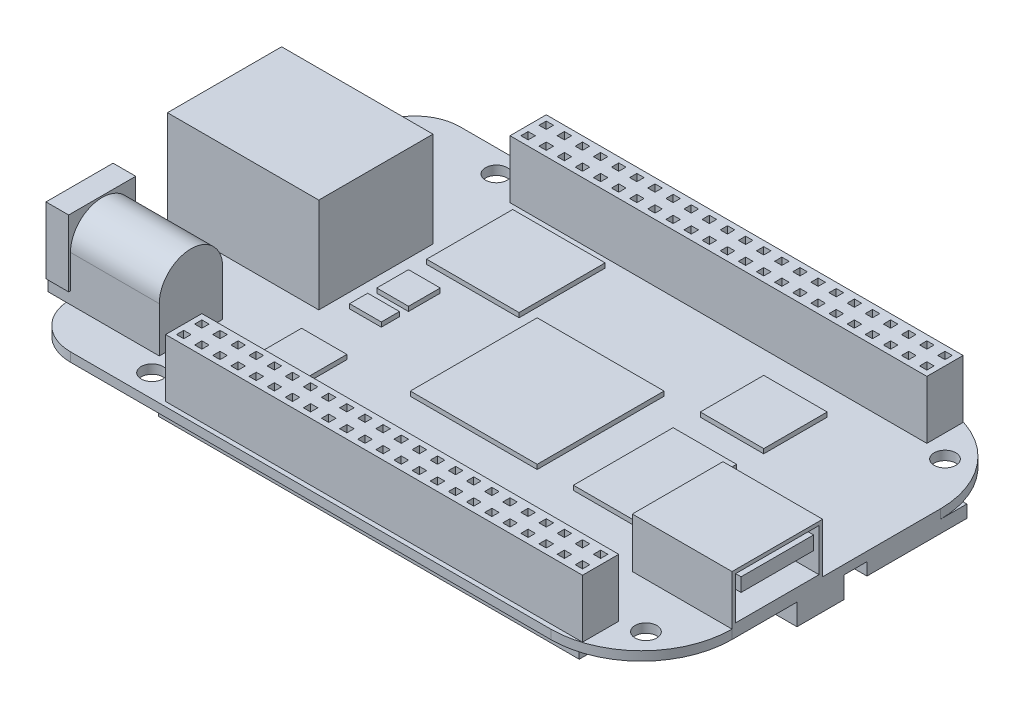
SolidWorks part; units mm, degrees
material "beaglebone"
ref_plane "Front Plane" through (0, 0, 0) normal (0, 0, 1) x (1, 0, 0)
ref_plane "Top Plane" through (0, 0, 0) normal (0, 1, 0) x (1, 0, 0)
ref_plane "Right Plane" through (0, 0, 0) normal (1, 0, 0) x (0, 0, -1)
sketch "Sketch1" plane through (0, 0, 0) normal (0, 1, 0) x (1, 0, 0)
  line L1 (-12.7, 0) -> (-80.01, 0)
  line L2 (0, 12.7) -> (0, 41.91)
  line L3 (-12.7, 54.61) -> (-80.01, 54.61)
  line L4 (-86.36, 6.35) -> (-86.36, 48.26)
  arc A0 (0, 12.7) -> (-12.7, 0) centre (-12.7, 12.7) cw
  arc A1 (0, 41.91) -> (-12.7, 54.61) centre (-12.7, 41.91) ccw
  arc A2 (-86.36, 6.35) -> (-80.01, 0) centre (-80.01, 6.35) ccw
  arc A3 (-86.36, 48.26) -> (-80.01, 54.61) centre (-80.01, 48.26) cw
  point P7 (0, 0)
  point P10 (0, 54.61)
  point P13 (-86.36, 0)
  dimension "D3" = 12.7
  dimension "D4" = 6.35
  dimension "D1" = 86.36
  dimension "D2" = 54.61
extrude "Boss-Extrude1" add sketch "Sketch1" along normal blind 1.27
sketch "Sketch2" plane through (0, 1.27, 0) normal (0, 1, 0) x (1, 0, 0)
  line L0 (-80.01, 0) -> (-12.7, 0) construction
  line L1 (-5.715, 6.35) -> (-71.755, 6.35) construction
  line L2 (-71.755, 51.435) -> (-71.755, 3.175) construction
  line L3 (-86.36, 48.26) -> (-86.36, 6.35) construction
  line L4 (-5.715, 48.26) -> (-5.715, 6.35) construction
  circle A0 centre (-71.755, 51.435) radius 1.524
  circle A1 centre (-71.755, 3.175) radius 1.524
  circle A2 centre (-5.715, 48.26) radius 1.524
  circle A3 centre (-5.715, 6.35) radius 1.524
  dimension "D7" = 3.048
  dimension "D1" = 48.26
  dimension "D2" = 41.91
  dimension "D3" = 6.35
  dimension "D4" = 14.605
  dimension "D5" = 80.645
  dimension "D6" = 3.175
extrude "Cut-Extrude1" cut sketch "Sketch2" along direction (0, -1, 0) on the side against the normal up to surface (1.27 mm away) up to face at (-44.4387, 0, -27.305)
sketch "Sketch3" plane through (0, 1.27, 0) normal (0, 1, 0) x (1, 0, 0)
  line L0 (-10.16, 48.895) -> (-10.16, 50.165) construction
  line L1 (-67.31, 53.975) -> (-8.89, 53.975)
  line L2 (-67.31, 53.975) -> (-67.31, 48.895)
  line L3 (-67.31, 48.895) -> (-8.89, 48.895)
  line L4 (-8.89, 53.975) -> (-8.89, 48.895)
  line L5 (-86.36, 27.305) -> (0, 27.305) construction
  line L6 (0, 12.7) -> (0, 41.91) construction
  line L7 (-66.548, 4.953) -> (-66.548, 3.937)
  line L8 (-66.548, 4.953) -> (-65.532, 4.953)
  line L9 (-10.16, 50.165) -> (-10.16, 52.705) construction
  line L10 (-10.16, 52.705) -> (-10.16, 53.975) construction
  line L11 (-13.208, 52.197) -> (-12.192, 52.197)
  line L12 (-10.668, 53.213) -> (-9.652, 53.213)
  line L13 (-10.668, 53.213) -> (-10.668, 52.197)
  line L14 (-10.668, 52.197) -> (-9.652, 52.197)
  line L15 (-9.652, 53.213) -> (-9.652, 52.197)
  line L16 (-10.668, 53.213) -> (-9.652, 52.197) construction
  line L17 (-10.668, 52.197) -> (-9.652, 53.213) construction
  line L18 (-10.668, 49.657) -> (-9.652, 49.657)
  line L19 (-10.668, 49.657) -> (-10.668, 50.673)
  line L20 (-10.668, 50.673) -> (-9.652, 50.673)
  line L21 (-9.652, 49.657) -> (-9.652, 50.673)
  line L22 (-10.668, 49.657) -> (-9.652, 50.673) construction
  line L23 (-10.668, 50.673) -> (-9.652, 49.657) construction
  line L24 (-13.208, 53.213) -> (-13.208, 52.197)
  line L25 (-13.208, 53.213) -> (-12.192, 53.213)
  line L26 (-12.192, 53.213) -> (-12.192, 52.197)
  line L27 (-13.208, 50.673) -> (-12.192, 50.673)
  line L28 (-12.192, 49.657) -> (-12.192, 50.673)
  line L29 (-13.208, 49.657) -> (-12.192, 49.657)
  line L30 (-13.208, 49.657) -> (-13.208, 50.673)
  line L31 (-15.748, 52.197) -> (-14.732, 52.197)
  line L32 (-15.748, 53.213) -> (-15.748, 52.197)
  line L33 (-15.748, 53.213) -> (-14.732, 53.213)
  line L34 (-14.732, 53.213) -> (-14.732, 52.197)
  line L35 (-15.748, 50.673) -> (-14.732, 50.673)
  line L36 (-14.732, 49.657) -> (-14.732, 50.673)
  line L37 (-15.748, 49.657) -> (-14.732, 49.657)
  line L38 (-15.748, 49.657) -> (-15.748, 50.673)
  line L39 (-18.288, 52.197) -> (-17.272, 52.197)
  line L40 (-18.288, 53.213) -> (-18.288, 52.197)
  line L41 (-18.288, 53.213) -> (-17.272, 53.213)
  line L42 (-17.272, 53.213) -> (-17.272, 52.197)
  line L43 (-18.288, 50.673) -> (-17.272, 50.673)
  line L44 (-17.272, 49.657) -> (-17.272, 50.673)
  line L45 (-18.288, 49.657) -> (-17.272, 49.657)
  line L46 (-18.288, 49.657) -> (-18.288, 50.673)
  line L47 (-20.828, 52.197) -> (-19.812, 52.197)
  line L48 (-20.828, 53.213) -> (-20.828, 52.197)
  line L49 (-20.828, 53.213) -> (-19.812, 53.213)
  line L50 (-19.812, 53.213) -> (-19.812, 52.197)
  line L51 (-20.828, 50.673) -> (-19.812, 50.673)
  line L52 (-19.812, 49.657) -> (-19.812, 50.673)
  line L53 (-20.828, 49.657) -> (-19.812, 49.657)
  line L54 (-20.828, 49.657) -> (-20.828, 50.673)
  line L55 (-23.368, 52.197) -> (-22.352, 52.197)
  line L56 (-23.368, 53.213) -> (-23.368, 52.197)
  line L57 (-23.368, 53.213) -> (-22.352, 53.213)
  line L58 (-22.352, 53.213) -> (-22.352, 52.197)
  line L59 (-23.368, 50.673) -> (-22.352, 50.673)
  line L60 (-22.352, 49.657) -> (-22.352, 50.673)
  line L61 (-23.368, 49.657) -> (-22.352, 49.657)
  line L62 (-23.368, 49.657) -> (-23.368, 50.673)
  line L63 (-25.908, 52.197) -> (-24.892, 52.197)
  line L64 (-25.908, 53.213) -> (-25.908, 52.197)
  line L65 (-25.908, 53.213) -> (-24.892, 53.213)
  line L66 (-24.892, 53.213) -> (-24.892, 52.197)
  line L67 (-25.908, 50.673) -> (-24.892, 50.673)
  line L68 (-24.892, 49.657) -> (-24.892, 50.673)
  line L69 (-25.908, 49.657) -> (-24.892, 49.657)
  line L70 (-25.908, 49.657) -> (-25.908, 50.673)
  line L71 (-28.448, 52.197) -> (-27.432, 52.197)
  line L72 (-28.448, 53.213) -> (-28.448, 52.197)
  line L73 (-28.448, 53.213) -> (-27.432, 53.213)
  line L74 (-27.432, 53.213) -> (-27.432, 52.197)
  line L75 (-28.448, 50.673) -> (-27.432, 50.673)
  line L76 (-27.432, 49.657) -> (-27.432, 50.673)
  line L77 (-28.448, 49.657) -> (-27.432, 49.657)
  line L78 (-28.448, 49.657) -> (-28.448, 50.673)
  line L79 (-30.988, 52.197) -> (-29.972, 52.197)
  line L80 (-30.988, 53.213) -> (-30.988, 52.197)
  line L81 (-30.988, 53.213) -> (-29.972, 53.213)
  line L82 (-29.972, 53.213) -> (-29.972, 52.197)
  line L83 (-30.988, 50.673) -> (-29.972, 50.673)
  line L84 (-29.972, 49.657) -> (-29.972, 50.673)
  line L85 (-30.988, 49.657) -> (-29.972, 49.657)
  line L86 (-30.988, 49.657) -> (-30.988, 50.673)
  line L87 (-33.528, 52.197) -> (-32.512, 52.197)
  line L88 (-33.528, 53.213) -> (-33.528, 52.197)
  line L89 (-33.528, 53.213) -> (-32.512, 53.213)
  line L90 (-32.512, 53.213) -> (-32.512, 52.197)
  line L91 (-33.528, 50.673) -> (-32.512, 50.673)
  line L92 (-32.512, 49.657) -> (-32.512, 50.673)
  line L93 (-33.528, 49.657) -> (-32.512, 49.657)
  line L94 (-33.528, 49.657) -> (-33.528, 50.673)
  line L95 (-36.068, 52.197) -> (-35.052, 52.197)
  line L96 (-36.068, 53.213) -> (-36.068, 52.197)
  line L97 (-36.068, 53.213) -> (-35.052, 53.213)
  line L98 (-35.052, 53.213) -> (-35.052, 52.197)
  line L99 (-36.068, 50.673) -> (-35.052, 50.673)
  line L100 (-35.052, 49.657) -> (-35.052, 50.673)
  line L101 (-36.068, 49.657) -> (-35.052, 49.657)
  line L102 (-36.068, 49.657) -> (-36.068, 50.673)
  line L103 (-38.608, 52.197) -> (-37.592, 52.197)
  line L104 (-38.608, 53.213) -> (-38.608, 52.197)
  line L105 (-38.608, 53.213) -> (-37.592, 53.213)
  line L106 (-37.592, 53.213) -> (-37.592, 52.197)
  line L107 (-38.608, 50.673) -> (-37.592, 50.673)
  line L108 (-37.592, 49.657) -> (-37.592, 50.673)
  line L109 (-38.608, 49.657) -> (-37.592, 49.657)
  line L110 (-38.608, 49.657) -> (-38.608, 50.673)
  line L111 (-41.148, 52.197) -> (-40.132, 52.197)
  line L112 (-41.148, 53.213) -> (-41.148, 52.197)
  line L113 (-41.148, 53.213) -> (-40.132, 53.213)
  line L114 (-40.132, 53.213) -> (-40.132, 52.197)
  line L115 (-41.148, 50.673) -> (-40.132, 50.673)
  line L116 (-40.132, 49.657) -> (-40.132, 50.673)
  line L117 (-41.148, 49.657) -> (-40.132, 49.657)
  line L118 (-41.148, 49.657) -> (-41.148, 50.673)
  line L119 (-43.688, 52.197) -> (-42.672, 52.197)
  line L120 (-43.688, 53.213) -> (-43.688, 52.197)
  line L121 (-43.688, 53.213) -> (-42.672, 53.213)
  line L122 (-42.672, 53.213) -> (-42.672, 52.197)
  line L123 (-43.688, 50.673) -> (-42.672, 50.673)
  line L124 (-42.672, 49.657) -> (-42.672, 50.673)
  line L125 (-43.688, 49.657) -> (-42.672, 49.657)
  line L126 (-43.688, 49.657) -> (-43.688, 50.673)
  line L127 (-46.228, 52.197) -> (-45.212, 52.197)
  line L128 (-46.228, 53.213) -> (-46.228, 52.197)
  line L129 (-46.228, 53.213) -> (-45.212, 53.213)
  line L130 (-45.212, 53.213) -> (-45.212, 52.197)
  line L131 (-46.228, 50.673) -> (-45.212, 50.673)
  line L132 (-45.212, 49.657) -> (-45.212, 50.673)
  line L133 (-46.228, 49.657) -> (-45.212, 49.657)
  line L134 (-46.228, 49.657) -> (-46.228, 50.673)
  line L135 (-48.768, 52.197) -> (-47.752, 52.197)
  line L136 (-48.768, 53.213) -> (-48.768, 52.197)
  line L137 (-48.768, 53.213) -> (-47.752, 53.213)
  line L138 (-47.752, 53.213) -> (-47.752, 52.197)
  line L139 (-48.768, 50.673) -> (-47.752, 50.673)
  line L140 (-47.752, 49.657) -> (-47.752, 50.673)
  line L141 (-48.768, 49.657) -> (-47.752, 49.657)
  line L142 (-48.768, 49.657) -> (-48.768, 50.673)
  line L143 (-51.308, 52.197) -> (-50.292, 52.197)
  line L144 (-51.308, 53.213) -> (-51.308, 52.197)
  line L145 (-51.308, 53.213) -> (-50.292, 53.213)
  line L146 (-50.292, 53.213) -> (-50.292, 52.197)
  line L147 (-51.308, 50.673) -> (-50.292, 50.673)
  line L148 (-50.292, 49.657) -> (-50.292, 50.673)
  line L149 (-51.308, 49.657) -> (-50.292, 49.657)
  line L150 (-51.308, 49.657) -> (-51.308, 50.673)
  line L151 (-53.848, 52.197) -> (-52.832, 52.197)
  line L152 (-53.848, 53.213) -> (-53.848, 52.197)
  line L153 (-53.848, 53.213) -> (-52.832, 53.213)
  line L154 (-52.832, 53.213) -> (-52.832, 52.197)
  line L155 (-53.848, 50.673) -> (-52.832, 50.673)
  line L156 (-52.832, 49.657) -> (-52.832, 50.673)
  line L157 (-53.848, 49.657) -> (-52.832, 49.657)
  line L158 (-53.848, 49.657) -> (-53.848, 50.673)
  line L159 (-56.388, 52.197) -> (-55.372, 52.197)
  line L160 (-56.388, 53.213) -> (-56.388, 52.197)
  line L161 (-56.388, 53.213) -> (-55.372, 53.213)
  line L162 (-55.372, 53.213) -> (-55.372, 52.197)
  line L163 (-56.388, 50.673) -> (-55.372, 50.673)
  line L164 (-55.372, 49.657) -> (-55.372, 50.673)
  line L165 (-56.388, 49.657) -> (-55.372, 49.657)
  line L166 (-56.388, 49.657) -> (-56.388, 50.673)
  line L167 (-58.928, 52.197) -> (-57.912, 52.197)
  line L168 (-58.928, 53.213) -> (-58.928, 52.197)
  line L169 (-58.928, 53.213) -> (-57.912, 53.213)
  line L170 (-57.912, 53.213) -> (-57.912, 52.197)
  line L171 (-58.928, 50.673) -> (-57.912, 50.673)
  line L172 (-57.912, 49.657) -> (-57.912, 50.673)
  line L173 (-58.928, 49.657) -> (-57.912, 49.657)
  line L174 (-58.928, 49.657) -> (-58.928, 50.673)
  line L175 (-61.468, 52.197) -> (-60.452, 52.197)
  line L176 (-61.468, 53.213) -> (-61.468, 52.197)
  line L177 (-61.468, 53.213) -> (-60.452, 53.213)
  line L178 (-60.452, 53.213) -> (-60.452, 52.197)
  line L179 (-61.468, 50.673) -> (-60.452, 50.673)
  line L180 (-60.452, 49.657) -> (-60.452, 50.673)
  line L181 (-61.468, 49.657) -> (-60.452, 49.657)
  line L182 (-61.468, 49.657) -> (-61.468, 50.673)
  line L183 (-64.008, 52.197) -> (-62.992, 52.197)
  line L184 (-64.008, 53.213) -> (-64.008, 52.197)
  line L185 (-64.008, 53.213) -> (-62.992, 53.213)
  line L186 (-62.992, 53.213) -> (-62.992, 52.197)
  line L187 (-64.008, 50.673) -> (-62.992, 50.673)
  line L188 (-62.992, 49.657) -> (-62.992, 50.673)
  line L189 (-64.008, 49.657) -> (-62.992, 49.657)
  line L190 (-64.008, 49.657) -> (-64.008, 50.673)
  line L191 (-66.548, 52.197) -> (-65.532, 52.197)
  line L192 (-66.548, 53.213) -> (-66.548, 52.197)
  line L193 (-66.548, 53.213) -> (-65.532, 53.213)
  line L194 (-65.532, 53.213) -> (-65.532, 52.197)
  line L195 (-66.548, 50.673) -> (-65.532, 50.673)
  line L196 (-65.532, 49.657) -> (-65.532, 50.673)
  line L197 (-66.548, 49.657) -> (-65.532, 49.657)
  line L198 (-66.548, 49.657) -> (-66.548, 50.673)
  line L199 (-66.548, 49.657) -> (-65.532, 50.673) construction
  line L200 (-86.36, 48.26) -> (-86.36, 6.35) construction
  line L201 (-65.532, 4.953) -> (-65.532, 3.937)
  line L202 (-12.7, 54.61) -> (-80.01, 54.61) construction
  line L203 (-66.548, 3.937) -> (-65.532, 3.937)
  line L204 (-65.532, 1.397) -> (-65.532, 2.413)
  line L205 (-66.548, 1.397) -> (-65.532, 1.397)
  line L206 (-66.548, 1.397) -> (-66.548, 2.413)
  line L207 (-66.548, 2.413) -> (-65.532, 2.413)
  line L208 (-64.008, 4.953) -> (-64.008, 3.937)
  line L209 (-64.008, 4.953) -> (-62.992, 4.953)
  line L210 (-62.992, 4.953) -> (-62.992, 3.937)
  line L211 (-64.008, 3.937) -> (-62.992, 3.937)
  line L212 (-62.992, 1.397) -> (-62.992, 2.413)
  line L213 (-64.008, 1.397) -> (-62.992, 1.397)
  line L214 (-64.008, 1.397) -> (-64.008, 2.413)
  line L215 (-64.008, 2.413) -> (-62.992, 2.413)
  line L216 (-61.468, 4.953) -> (-61.468, 3.937)
  line L217 (-61.468, 4.953) -> (-60.452, 4.953)
  line L218 (-60.452, 4.953) -> (-60.452, 3.937)
  line L219 (-61.468, 3.937) -> (-60.452, 3.937)
  line L220 (-60.452, 1.397) -> (-60.452, 2.413)
  line L221 (-61.468, 1.397) -> (-60.452, 1.397)
  line L222 (-61.468, 1.397) -> (-61.468, 2.413)
  line L223 (-61.468, 2.413) -> (-60.452, 2.413)
  line L224 (-58.928, 4.953) -> (-58.928, 3.937)
  line L225 (-58.928, 4.953) -> (-57.912, 4.953)
  line L226 (-57.912, 4.953) -> (-57.912, 3.937)
  line L227 (-58.928, 3.937) -> (-57.912, 3.937)
  line L228 (-57.912, 1.397) -> (-57.912, 2.413)
  line L229 (-58.928, 1.397) -> (-57.912, 1.397)
  line L230 (-58.928, 1.397) -> (-58.928, 2.413)
  line L231 (-58.928, 2.413) -> (-57.912, 2.413)
  line L232 (-56.388, 4.953) -> (-56.388, 3.937)
  line L233 (-56.388, 4.953) -> (-55.372, 4.953)
  line L234 (-55.372, 4.953) -> (-55.372, 3.937)
  line L235 (-56.388, 3.937) -> (-55.372, 3.937)
  line L236 (-55.372, 1.397) -> (-55.372, 2.413)
  line L237 (-56.388, 1.397) -> (-55.372, 1.397)
  line L238 (-56.388, 1.397) -> (-56.388, 2.413)
  line L239 (-56.388, 2.413) -> (-55.372, 2.413)
  line L240 (-53.848, 4.953) -> (-53.848, 3.937)
  line L241 (-53.848, 4.953) -> (-52.832, 4.953)
  line L242 (-52.832, 4.953) -> (-52.832, 3.937)
  line L243 (-53.848, 3.937) -> (-52.832, 3.937)
  line L244 (-52.832, 1.397) -> (-52.832, 2.413)
  line L245 (-53.848, 1.397) -> (-52.832, 1.397)
  line L246 (-53.848, 1.397) -> (-53.848, 2.413)
  line L247 (-53.848, 2.413) -> (-52.832, 2.413)
  line L248 (-51.308, 4.953) -> (-51.308, 3.937)
  line L249 (-51.308, 4.953) -> (-50.292, 4.953)
  line L250 (-50.292, 4.953) -> (-50.292, 3.937)
  line L251 (-51.308, 3.937) -> (-50.292, 3.937)
  line L252 (-50.292, 1.397) -> (-50.292, 2.413)
  line L253 (-51.308, 1.397) -> (-50.292, 1.397)
  line L254 (-51.308, 1.397) -> (-51.308, 2.413)
  line L255 (-51.308, 2.413) -> (-50.292, 2.413)
  line L256 (-48.768, 4.953) -> (-48.768, 3.937)
  line L257 (-48.768, 4.953) -> (-47.752, 4.953)
  line L258 (-47.752, 4.953) -> (-47.752, 3.937)
  line L259 (-48.768, 3.937) -> (-47.752, 3.937)
  line L260 (-47.752, 1.397) -> (-47.752, 2.413)
  line L261 (-48.768, 1.397) -> (-47.752, 1.397)
  line L262 (-48.768, 1.397) -> (-48.768, 2.413)
  line L263 (-48.768, 2.413) -> (-47.752, 2.413)
  line L264 (-46.228, 4.953) -> (-46.228, 3.937)
  line L265 (-46.228, 4.953) -> (-45.212, 4.953)
  line L266 (-45.212, 4.953) -> (-45.212, 3.937)
  line L267 (-46.228, 3.937) -> (-45.212, 3.937)
  line L268 (-45.212, 1.397) -> (-45.212, 2.413)
  line L269 (-46.228, 1.397) -> (-45.212, 1.397)
  line L270 (-46.228, 1.397) -> (-46.228, 2.413)
  line L271 (-46.228, 2.413) -> (-45.212, 2.413)
  line L272 (-43.688, 4.953) -> (-43.688, 3.937)
  line L273 (-43.688, 4.953) -> (-42.672, 4.953)
  line L274 (-42.672, 4.953) -> (-42.672, 3.937)
  line L275 (-43.688, 3.937) -> (-42.672, 3.937)
  line L276 (-42.672, 1.397) -> (-42.672, 2.413)
  line L277 (-43.688, 1.397) -> (-42.672, 1.397)
  line L278 (-43.688, 1.397) -> (-43.688, 2.413)
  line L279 (-43.688, 2.413) -> (-42.672, 2.413)
  line L280 (-41.148, 4.953) -> (-41.148, 3.937)
  line L281 (-41.148, 4.953) -> (-40.132, 4.953)
  line L282 (-40.132, 4.953) -> (-40.132, 3.937)
  line L283 (-41.148, 3.937) -> (-40.132, 3.937)
  line L284 (-40.132, 1.397) -> (-40.132, 2.413)
  line L285 (-41.148, 1.397) -> (-40.132, 1.397)
  line L286 (-41.148, 1.397) -> (-41.148, 2.413)
  line L287 (-41.148, 2.413) -> (-40.132, 2.413)
  line L288 (-38.608, 4.953) -> (-38.608, 3.937)
  line L289 (-38.608, 4.953) -> (-37.592, 4.953)
  line L290 (-37.592, 4.953) -> (-37.592, 3.937)
  line L291 (-38.608, 3.937) -> (-37.592, 3.937)
  line L292 (-37.592, 1.397) -> (-37.592, 2.413)
  line L293 (-38.608, 1.397) -> (-37.592, 1.397)
  line L294 (-38.608, 1.397) -> (-38.608, 2.413)
  line L295 (-38.608, 2.413) -> (-37.592, 2.413)
  line L296 (-36.068, 4.953) -> (-36.068, 3.937)
  line L297 (-36.068, 4.953) -> (-35.052, 4.953)
  line L298 (-35.052, 4.953) -> (-35.052, 3.937)
  line L299 (-36.068, 3.937) -> (-35.052, 3.937)
  line L300 (-35.052, 1.397) -> (-35.052, 2.413)
  line L301 (-36.068, 1.397) -> (-35.052, 1.397)
  line L302 (-36.068, 1.397) -> (-36.068, 2.413)
  line L303 (-36.068, 2.413) -> (-35.052, 2.413)
  line L304 (-33.528, 4.953) -> (-33.528, 3.937)
  line L305 (-33.528, 4.953) -> (-32.512, 4.953)
  line L306 (-32.512, 4.953) -> (-32.512, 3.937)
  line L307 (-33.528, 3.937) -> (-32.512, 3.937)
  line L308 (-32.512, 1.397) -> (-32.512, 2.413)
  line L309 (-33.528, 1.397) -> (-32.512, 1.397)
  line L310 (-33.528, 1.397) -> (-33.528, 2.413)
  line L311 (-33.528, 2.413) -> (-32.512, 2.413)
  line L312 (-30.988, 4.953) -> (-30.988, 3.937)
  line L313 (-30.988, 4.953) -> (-29.972, 4.953)
  line L314 (-29.972, 4.953) -> (-29.972, 3.937)
  line L315 (-30.988, 3.937) -> (-29.972, 3.937)
  line L316 (-29.972, 1.397) -> (-29.972, 2.413)
  line L317 (-30.988, 1.397) -> (-29.972, 1.397)
  line L318 (-30.988, 1.397) -> (-30.988, 2.413)
  line L319 (-30.988, 2.413) -> (-29.972, 2.413)
  line L320 (-28.448, 4.953) -> (-28.448, 3.937)
  line L321 (-28.448, 4.953) -> (-27.432, 4.953)
  line L322 (-27.432, 4.953) -> (-27.432, 3.937)
  line L323 (-28.448, 3.937) -> (-27.432, 3.937)
  line L324 (-27.432, 1.397) -> (-27.432, 2.413)
  line L325 (-28.448, 1.397) -> (-27.432, 1.397)
  line L326 (-28.448, 1.397) -> (-28.448, 2.413)
  line L327 (-28.448, 2.413) -> (-27.432, 2.413)
  line L328 (-25.908, 4.953) -> (-25.908, 3.937)
  line L329 (-25.908, 4.953) -> (-24.892, 4.953)
  line L330 (-24.892, 4.953) -> (-24.892, 3.937)
  line L331 (-25.908, 3.937) -> (-24.892, 3.937)
  line L332 (-24.892, 1.397) -> (-24.892, 2.413)
  line L333 (-25.908, 1.397) -> (-24.892, 1.397)
  line L334 (-25.908, 1.397) -> (-25.908, 2.413)
  line L335 (-25.908, 2.413) -> (-24.892, 2.413)
  line L336 (-23.368, 4.953) -> (-23.368, 3.937)
  line L337 (-23.368, 4.953) -> (-22.352, 4.953)
  line L338 (-22.352, 4.953) -> (-22.352, 3.937)
  line L339 (-23.368, 3.937) -> (-22.352, 3.937)
  line L340 (-22.352, 1.397) -> (-22.352, 2.413)
  line L341 (-23.368, 1.397) -> (-22.352, 1.397)
  line L342 (-23.368, 1.397) -> (-23.368, 2.413)
  line L343 (-23.368, 2.413) -> (-22.352, 2.413)
  line L344 (-20.828, 4.953) -> (-20.828, 3.937)
  line L345 (-20.828, 4.953) -> (-19.812, 4.953)
  line L346 (-19.812, 4.953) -> (-19.812, 3.937)
  line L347 (-20.828, 3.937) -> (-19.812, 3.937)
  line L348 (-19.812, 1.397) -> (-19.812, 2.413)
  line L349 (-20.828, 1.397) -> (-19.812, 1.397)
  line L350 (-20.828, 1.397) -> (-20.828, 2.413)
  line L351 (-20.828, 2.413) -> (-19.812, 2.413)
  line L352 (-18.288, 4.953) -> (-18.288, 3.937)
  line L353 (-18.288, 4.953) -> (-17.272, 4.953)
  line L354 (-17.272, 4.953) -> (-17.272, 3.937)
  line L355 (-18.288, 3.937) -> (-17.272, 3.937)
  line L356 (-17.272, 1.397) -> (-17.272, 2.413)
  line L357 (-18.288, 1.397) -> (-17.272, 1.397)
  line L358 (-18.288, 1.397) -> (-18.288, 2.413)
  line L359 (-18.288, 2.413) -> (-17.272, 2.413)
  line L360 (-15.748, 4.953) -> (-15.748, 3.937)
  line L361 (-15.748, 4.953) -> (-14.732, 4.953)
  line L362 (-14.732, 4.953) -> (-14.732, 3.937)
  line L363 (-15.748, 3.937) -> (-14.732, 3.937)
  line L364 (-14.732, 1.397) -> (-14.732, 2.413)
  line L365 (-15.748, 1.397) -> (-14.732, 1.397)
  line L366 (-15.748, 1.397) -> (-15.748, 2.413)
  line L367 (-15.748, 2.413) -> (-14.732, 2.413)
  line L368 (-13.208, 4.953) -> (-13.208, 3.937)
  line L369 (-13.208, 4.953) -> (-12.192, 4.953)
  line L370 (-12.192, 4.953) -> (-12.192, 3.937)
  line L371 (-13.208, 3.937) -> (-12.192, 3.937)
  line L372 (-12.192, 1.397) -> (-12.192, 2.413)
  line L373 (-13.208, 1.397) -> (-12.192, 1.397)
  line L374 (-13.208, 1.397) -> (-13.208, 2.413)
  line L375 (-9.652, 4.953) -> (-9.652, 3.937)
  line L376 (-10.668, 3.937) -> (-9.652, 3.937)
  line L377 (-10.668, 4.953) -> (-10.668, 3.937)
  line L378 (-10.668, 4.953) -> (-9.652, 4.953)
  line L379 (-9.652, 1.397) -> (-9.652, 2.413)
  line L380 (-10.668, 2.413) -> (-9.652, 2.413)
  line L381 (-10.668, 1.397) -> (-10.668, 2.413)
  line L382 (-10.668, 1.397) -> (-9.652, 1.397)
  line L383 (-13.208, 2.413) -> (-12.192, 2.413)
  line L384 (-8.89, 0.635) -> (-8.89, 5.715)
  line L385 (-67.31, 5.715) -> (-8.89, 5.715)
  line L386 (-67.31, 0.635) -> (-67.31, 5.715)
  line L387 (-67.31, 0.635) -> (-8.89, 0.635)
  circle A0 centre (-66.04, 50.165) radius 0.1361
  dimension "D1" = 1.016
  dimension "D2" = 2.54
  dimension "D3" = 5.08
  dimension "D4" = 58.42
  dimension "D5" = 1.27
  dimension "D7" = 20.32
  dimension "D8" = 0.635
  dimension "D6" = 23
extrude "Boss-Extrude2" add sketch "Sketch3" along normal blind 8.128 contours L4 L1 L2 L3 L193 L194 L191 L192 L185 L186 L183 L184 L177 L178 L175 L176 L169 L170 L167 L168 L161 L162 L159 L160 L153 L154 L151 L152 L145 L146 L143 L144 L137 L138 L135 L136 L129 L130 L127 L128 L121 | L386 L387 L384 L385 L374 L383 L372 L373 L382 L381 L380 L379 L366 L367 L364 L365 L363 L360 L361 L362 L350 L351 L348 L349 L347 L344 L345 L346 L334 L335 L332 L333 L331 L328 L329 L330 L318 L319 L316 L317 L315 region at (-38.1, 1.27, -51.435) region at (-38.1, 1.27, -3.175)
sketch "Sketch4" plane through (0, 1.27, 0) normal (0, 1, 0) x (1, 0, 0)
  line L0 (-86.36, 48.26) -> (-86.36, 6.35) construction
  line L1 (-67.691, 22.479) -> (-88.9, 22.479)
  line L2 (-67.691, 22.479) -> (-67.691, 38.481)
  line L3 (-67.691, 38.481) -> (-88.9, 38.481)
  line L4 (-88.9, 22.479) -> (-88.9, 38.481)
  line L5 (-12.7, 54.61) -> (-80.01, 54.61) construction
  dimension "D1" = 2.54
  dimension "D2" = 21.209
  dimension "D3" = 16.002
  dimension "D4" = 16.129
extrude "Boss-Extrude3" add sketch "Sketch4" along normal blind 13.335
sketch "Sketch5" plane through (-88.9, 0, 0) normal (-1, 0, 0) x (0, 0, 1)
  line L0 (-30.48, 2.286) -> (-30.48, 3.937) construction
  line L1 (-36.83, 12.065) -> (-24.13, 12.065)
  line L2 (-36.83, 12.065) -> (-36.83, 5.461)
  line L3 (-36.83, 5.461) -> (-24.13, 5.461)
  line L4 (-24.13, 12.065) -> (-24.13, 5.461)
  line L5 (-33.655, 5.461) -> (-27.305, 5.461)
  line L6 (-33.655, 5.461) -> (-33.655, 3.937)
  line L7 (-33.655, 3.937) -> (-27.305, 3.937)
  line L8 (-27.305, 5.461) -> (-27.305, 3.937)
  line L9 (-32.512, 3.937) -> (-28.448, 3.937)
  line L10 (-32.512, 3.937) -> (-32.512, 2.286)
  line L11 (-32.512, 2.286) -> (-28.448, 2.286)
  line L12 (-28.448, 3.937) -> (-28.448, 2.286)
  line L13 (-30.48, 3.937) -> (-30.48, 5.461) construction
  line L14 (-38.481, 14.605) -> (-22.479, 14.605) construction
  line L15 (-36.83, 12.065) -> (-38.481, 12.065) construction
  line L16 (-38.481, 14.605) -> (-38.481, 1.27) construction
  line L17 (-24.13, 12.065) -> (-22.479, 12.065) construction
  line L18 (-22.479, 14.605) -> (-22.479, 1.27) construction
  dimension "D1" = 12.7
  dimension "D2" = 6.604
  dimension "D3" = 2.54
  dimension "D4" = 1.524
  dimension "D5" = 1.651
  dimension "D6" = 4.064
  dimension "D7" = 6.35
extrude "Cut-Extrude2" cut sketch "Sketch5" against normal blind 17.78 contours L4 L1 L2 L3 | L8 L3 L6 L7 | L12 L7 L10 L11 region at (-88.9, 8.763, -30.48) region at (-88.9, 4.699, -30.48) region at (-88.9, 3.1115, -30.48)
sketch "Sketch6" plane through (0, 1.27, 0) normal (0, 1, 0) x (1, 0, 0)
  line L0 (-67.31, 48.895) -> (-8.89, 48.895) construction
  line L1 (-65.659, 35.56) -> (-52.705, 35.56)
  line L2 (-65.659, 35.56) -> (-65.659, 47.625)
  line L3 (-65.659, 47.625) -> (-52.705, 47.625)
  line L4 (-52.705, 35.56) -> (-52.705, 47.625)
  line L5 (-50.8, 36.195) -> (-33.02, 36.195)
  line L6 (-50.8, 36.195) -> (-50.8, 18.415)
  line L7 (-50.8, 18.415) -> (-33.02, 18.415)
  line L8 (-33.02, 36.195) -> (-33.02, 18.415)
  line L9 (-27.94, 45.085) -> (-19.05, 45.085)
  line L10 (-27.94, 45.085) -> (-27.94, 36.195)
  line L11 (-27.94, 36.195) -> (-19.05, 36.195)
  line L12 (-19.05, 45.085) -> (-19.05, 36.195)
  line L13 (-27.94, 32.385) -> (-19.05, 32.385)
  line L14 (-27.94, 32.385) -> (-27.94, 18.415)
  line L15 (-27.94, 18.415) -> (-19.05, 18.415)
  line L16 (-19.05, 32.385) -> (-19.05, 18.415)
  line L17 (-66.04, 18.415) -> (-59.69, 18.415)
  line L18 (-66.04, 18.415) -> (-66.04, 12.065)
  line L19 (-66.04, 12.065) -> (-59.69, 12.065)
  line L20 (-59.69, 18.415) -> (-59.69, 12.065)
  line L21 (-65.659, 27.305) -> (-61.214, 27.305)
  line L22 (-65.659, 27.305) -> (-65.659, 24.765)
  line L23 (-65.659, 24.765) -> (-61.214, 24.765)
  line L24 (-61.214, 27.305) -> (-61.214, 24.765)
  line L25 (-65.659, 33.02) -> (-61.214, 33.02)
  line L26 (-65.659, 33.02) -> (-65.659, 28.575)
  line L27 (-65.659, 28.575) -> (-61.214, 28.575)
  line L28 (-61.214, 33.02) -> (-61.214, 28.575)
  line L29 (0, 12.7) -> (0, 41.91) construction
  line L30 (-67.31, 48.895) -> (-8.89, 48.895) construction
  line L31 (-67.31, 5.715) -> (-8.89, 5.715) construction
  line L33 (-67.31, 0.635) -> (-67.31, 5.715) construction
  dimension "D1" = 8.89
  dimension "D2" = 13.97
  dimension "D3" = 3.81
  dimension "D4" = 3.81
  dimension "D5" = 19.05
  dimension "D6" = 17.78
  dimension "D7" = 12.7
  dimension "D8" = 33.02
  dimension "D9" = 12.954
  dimension "D10" = 12.065
  dimension "D11" = 1.905
  dimension "D12" = 4.445
  dimension "D13" = 2.54
  dimension "D14" = 1.27
  dimension "D15" = 2.54
  dimension "D16" = 1.27
  dimension "D17" = 6.35
  dimension "D18" = 6.35
  dimension "D19" = 1.27
extrude "Boss-Extrude4" add sketch "Sketch6" along normal blind 0.635
sketch "Sketch7" plane through (0, 1.27, 0) normal (0, 1, 0) x (1, 0, 0)
  line L1 (0, 12.7) -> (-13.97, 12.7)
  line L2 (0, 12.7) -> (0, 25.4)
  line L3 (0, 25.4) -> (-13.97, 25.4)
  line L4 (-13.97, 12.7) -> (-13.97, 25.4)
  line L5 (-80.01, 0) -> (-12.7, 0) construction
  line L6 (0, 12.7) -> (0, 41.91) construction
  dimension "D1" = 12.7
  dimension "D2" = 13.97
  dimension "D3" = 25.4
extrude "Boss-Extrude5" add sketch "Sketch7" along normal blind 6.985
sketch "Sketch8" plane through (0, 0, 0) normal (1, 0, 0) x (0, 0, -1)
  line L0 (12.7, 8.255) -> (25.4, 8.255) construction
  line L1 (13.97, 6.985) -> (24.13, 6.985)
  line L2 (13.97, 6.985) -> (13.97, 5.08)
  line L3 (13.97, 5.08) -> (24.13, 5.08)
  line L4 (24.13, 6.985) -> (24.13, 5.08)
  line L5 (13.208, 7.747) -> (24.892, 7.747)
  line L6 (13.208, 7.747) -> (13.208, 1.778)
  line L7 (13.208, 1.778) -> (24.892, 1.778)
  line L8 (24.892, 7.747) -> (24.892, 1.778)
  line L9 (25.4, 8.255) -> (25.4, 1.27) construction
  line L10 (12.7, 8.255) -> (12.7, 1.27) construction
  line L11 (12.7, 1.27) -> (0, 1.27) construction
  line L12 (13.97, 7.18) -> (13.208, 7.18) construction
  line L14 (24.892, 6.9479) -> (24.13, 6.9479) construction
  dimension "D1" = 0.508
  dimension "D2" = 0.508
  dimension "D3" = 0.508
  dimension "D4" = 0.508
  dimension "D5" = 1.905
  dimension "D6" = 10.16
  dimension "D7" = 3.175
extrude "Cut-Extrude3" cut sketch "Sketch8" against normal blind 12.7
sketch "Sketch9" plane through (0, 1.27, 0) normal (0, 1, 0) x (1, 0, 0)
  line L0 (-88.9, 38.481) -> (-88.9, 22.479) construction
  line L1 (-73.279, 5.715) -> (-88.9, 5.715)
  line L2 (-73.279, 5.715) -> (-73.279, 14.605)
  line L3 (-73.279, 14.605) -> (-88.9, 14.605)
  line L4 (-88.9, 5.715) -> (-88.9, 14.605)
  line L5 (-67.31, 5.715) -> (-8.89, 5.715) construction
  circle A0 centre (-71.755, 3.175) radius 1.524 construction
  dimension "D1" = 8.89
extrude "Boss-Extrude6" add sketch "Sketch9" along normal blind 6.35
sketch "Sketch10" plane through (-88.9, 0, 0) normal (-1, 0, 0) x (0, 0, 1)
  line L0 (-14.605, 7.62) -> (-5.715, 7.62) construction
  circle A0 centre (-10.16, 7.62) radius 4.445
  circle A1 centre (-10.16, 7.62) radius 3.4925
  circle A2 centre (-10.16, 7.62) radius 0.635
  line M3 (-5.715, 7.62) -> (-14.605, 7.62)
  dimension "D1" = 1.27
  dimension "D2" = 6.985
extrude "Boss-Extrude7" add sketch "Sketch10" along direction (1, 0, 0) on the side against the normal up to surface (15.621 mm away) contours A1 A0 M3 | A1 A0 M3 | A2 M3 | A2 A1 M3 region at (-88.9, 7.7194, -6.1912) region at (-88.9, 3.2744, -10.16) region at (-88.9, 9.1437, -10.16) region at (-88.9, 7.8895, -10.16) up to face at (-73.279, 4.445, -10.16)
sketch "Sketch11" plane through (-88.9, 0, 0) normal (-1, 0, 0) x (0, 0, 1)
  line L0 (-14.605, 7.62) -> (-14.605, 1.27) construction
  line L1 (-5.461, 2.952) -> (-14.859, 2.952)
  line L2 (-5.461, 2.952) -> (-5.461, 12.288)
  line L3 (-5.461, 12.288) -> (-14.859, 12.288)
  line L4 (-14.859, 2.952) -> (-14.859, 12.288)
  line L5 (-5.461, 2.952) -> (-14.859, 12.288) construction
  line L6 (-5.461, 12.288) -> (-14.859, 2.952) construction
  point P0 (-10.16, 7.62)
  dimension "D1" = 0.254
extrude "Boss-Extrude8" add sketch "Sketch11" against normal blind 3.175
extrude "Cut-Extrude4" cut sketch "Sketch10<3>" against normal blind 12.7 contours A2 A1 M3 | A2 A1 M3 region at (-88.9, 9.1437, -10.16) region at (-88.9, 6.0963, -10.16)
sketch "Sketch10<3>" plane through (-88.9, 0, 0) normal (-1, 0, 0) x (0, 0, 1) same geometry as "Sketch10"
fillet "Fillet1" radius 0.635 1 edges at (-88.9, 7.62, -9.525)
ref_plane "MidPlane" through (-43.18, 0, 0) normal (-1, 0, 0) x (0, 0, 1)
ref_plane "Vertical Plane" through (0, 0, -27.305) normal (0, 0, 1) x (1, 0, 0)
sketch "Sketch12" plane through (0, 0, 0) normal (0, -1, 0) x (1, 0, 0)
  line L1 (-68.255, -5.6) -> (-9.315, -5.6)
  line L2 (-68.255, -5.6) -> (-68.255, -0.6)
  line L3 (-68.255, -0.6) -> (-9.315, -0.6)
  line L4 (-9.315, -5.6) -> (-9.315, -0.6)
  line L5 (-68.255, -5.6) -> (-9.315, -0.6) construction
  line L6 (-68.255, -0.6) -> (-9.315, -5.6) construction
  line L7 (-80.01, 0) -> (-12.7, 0) construction
  line L8 (-12.7, -54.61) -> (-80.01, -54.61) construction
  line L9 (-15, -31.61) -> (0, -31.61)
  line L10 (-15, -31.61) -> (-15, -45.61)
  line L11 (-15, -45.61) -> (0, -45.61)
  line L12 (0, -31.61) -> (0, -45.61)
  line L13 (0, -12.7) -> (0, -41.91) construction
  line L14 (-1000, -27.305) -> (49000, -27.305) construction
  line L15 (-68.255, -49.01) -> (-9.315, -54.01) construction
  line L16 (-68.255, -54.01) -> (-9.315, -49.01) construction
  line L17 (-68.255, -49.01) -> (-68.255, -54.01)
  line L18 (-68.255, -49.01) -> (-9.315, -49.01)
  line L19 (-9.315, -49.01) -> (-9.315, -54.01)
  line L20 (-68.255, -54.01) -> (-9.315, -54.01)
  circle A0 centre (-5.715, -6.35) radius 1.524 construction
  circle A1 centre (-71.755, -3.175) radius 1.524 construction
  point P0 (-38.785, -3.1)
  point P22 (0, -27.305)
  dimension "D1" = 3.6
  dimension "D7" = 3.5
  dimension "D2" = 0.6
  dimension "D3" = 5
  dimension "D4" = 9
  dimension "D5" = 14
  dimension "D6" = 15
extrude "Boss-Extrude9" add sketch "Sketch12" along normal blind 1 contours L1 L4 L3 L2 | L17 L20 L19 L18 region at (-38.785, 0, -3.1) region at (-38.785, 0, -51.51)
extrude "Boss-Extrude10" add sketch "Sketch12<3>" along normal blind 1.75 contours L12 L11 L10 L9
sketch "Sketch12<3>" plane through (0, 0, 0) normal (0, -1, 0) x (1, 0, 0) same geometry as "Sketch12"
sketch "Sketch13" plane through (0, 0, 0) normal (0, -1, 0) x (1, 0, 0)
  line L0 (0, -12.7) -> (0, -31.61) construction
  line L1 (0, -21.8) -> (-7.7, -21.8)
  line L2 (0, -21.8) -> (0, -28.4)
  line L3 (0, -28.4) -> (-7.7, -28.4)
  line L4 (-7.7, -21.8) -> (-7.7, -28.4)
  line L5 (-80.01, 0) -> (-12.7, 0) construction
  dimension "D1" = 21.8
  dimension "D2" = 6.6
  dimension "D3" = 7.7
extrude "Boss-Extrude11" add sketch "Sketch13" along normal blind 3
